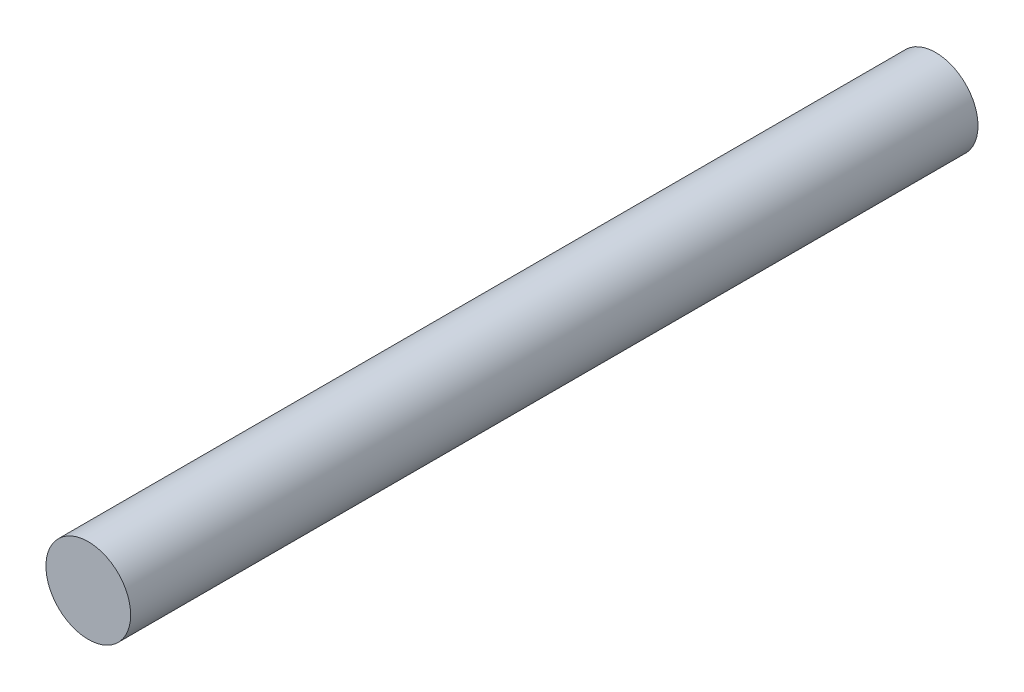
SolidWorks part; units mm, degrees
ref_plane "Front Plane" through (0, 0, 0) normal (0, 0, 1) x (1, 0, 0)
ref_plane "Top Plane" through (0, 0, 0) normal (0, 1, 0) x (1, 0, 0)
ref_plane "Right Plane" through (0, 0, 0) normal (1, 0, 0) x (0, 0, -1)
sketch "Sketch1" plane through (0, 0, 0) normal (0, 0, 1) x (1, 0, 0)
  circle A0 centre (0, 0) radius 12.7
extrude "Boss-Extrude1" add sketch "Sketch1" along normal mid plane 254 contours A0
